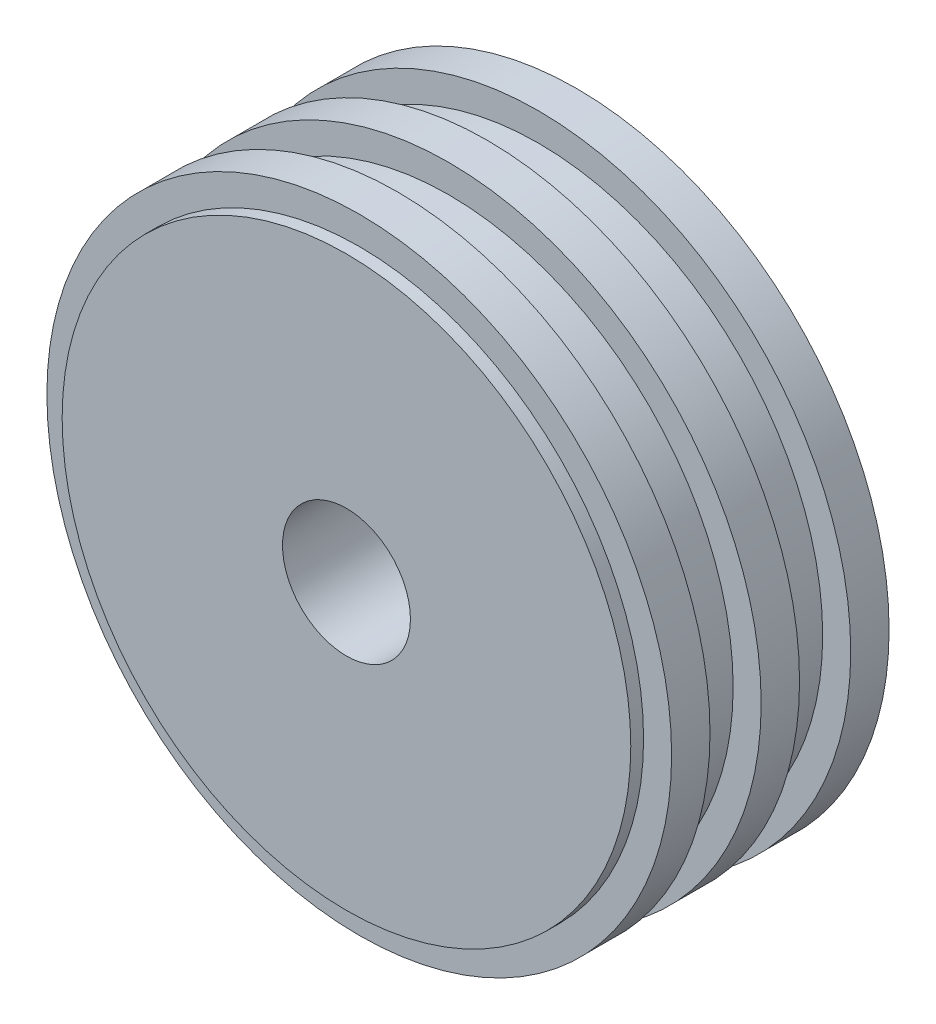
SolidWorks part; units mm, degrees
ref_plane "Front Plane" through (0, 0, 0) normal (0, 0, 1) x (1, 0, 0)
ref_plane "Top Plane" through (0, 0, 0) normal (0, 1, 0) x (1, 0, 0)
ref_plane "Right Plane" through (0, 0, 0) normal (1, 0, 0) x (0, 0, -1)
sketch "Sketch1" plane through (0, 0, 0) normal (0, 0, 1) x (1, 0, 0)
  circle A0 centre (0, 0) radius 15
  circle A1 centre (0, 0) radius 66.675
  dimension "D1" = 133.35
  dimension "D2" = 30
extrude "Boss-Extrude1" add sketch "Sketch1" against normal blind 57
ref_plane "Plane1" through (0, 0, -3) normal (0, 0, 1) x (1, 0, 0)
sketch "Sketch2" plane through (0, 0, -3) normal (0, 0, 1) x (1, 0, 0)
  circle A0 centre (0, 0) radius 66.675 construction
  circle A1 centre (0, 0) radius 66.675
  circle A2 centre (0, 0) radius 73.25
  dimension "D1" = 146.5
extrude "Boss-Extrude2" add sketch "Sketch2" against normal blind 9
ref_axis "Axis1" through (0, 0, -57) along (0, 0, 1)
pattern_linear "LPattern1" count 3 spacing 21 along (0, 0, -1) of "Boss-Extrude2"
